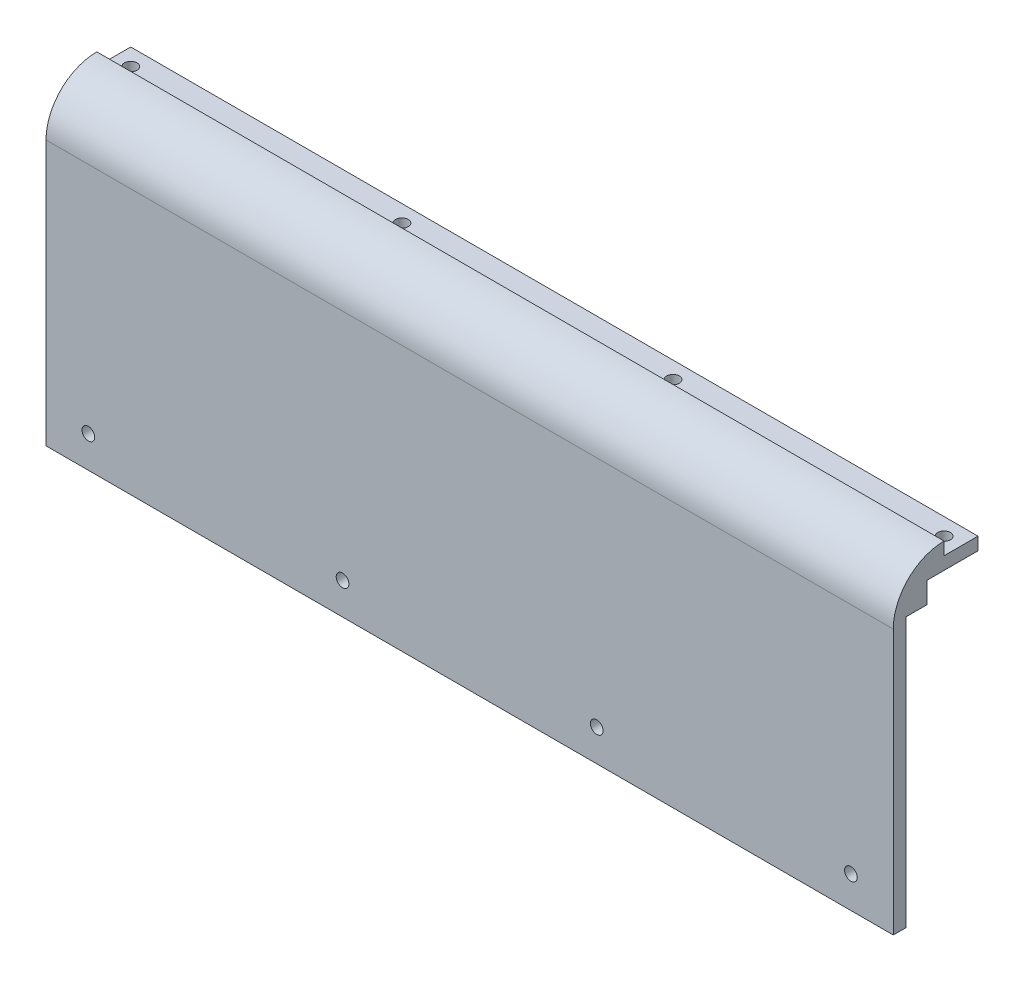
SolidWorks part; units mm, degrees
ref_plane "Front Plane" through (0, 0, 0) normal (0, 0, 1) x (1, 0, 0)
ref_plane "Top Plane" through (0, 0, 0) normal (0, 1, 0) x (1, 0, 0)
ref_plane "Right Plane" through (0, 0, 0) normal (1, 0, 0) x (0, 0, -1)
sketch "Sketch1" plane through (0, 0, 0) normal (0, 1, 0) x (1, 0, 0)
  line L1 (-100, -10) -> (100, -10)
  line L2 (-100, -10) -> (-100, 10)
  line L3 (-100, 10) -> (100, 10)
  line L4 (100, -10) -> (100, 10)
  line L5 (-100, -10) -> (100, 10) construction
  line L6 (-100, 10) -> (100, -10) construction
  point P0 (0, 0)
  dimension "D1" = 200
  dimension "D2" = 20
extrude "Boss-Extrude1" add sketch "Sketch1" along normal blind 3
sketch "Sketch2" plane through (0, 3, 0) normal (0, 1, 0) x (1, 0, 0)
  line L0 (100, 10) -> (-100, 10) construction
  line L1 (-100, 10) -> (-100, -10) construction
  circle A0 centre (-96, 6) radius 1.5
  dimension "D1" = 3
  dimension "D2" = 4
  dimension "D3" = 4
extrude "Cut-Extrude1" cut sketch "Sketch2" against normal up to next
pattern_linear "LPattern1" count 4 spacing 64 along (1, 0, 0) of "Cut-Extrude1"
sketch "Sketch3" plane through (0, 0, 0) normal (0, -1, 0) x (1, 0, 0)
  line L0 (100, 10) -> (100, -10) construction
  line L1 (-100, 10) -> (100, 10)
  line L2 (-100, 10) -> (-100, 7)
  line L3 (-100, 7) -> (100, 7)
  line L4 (100, 10) -> (100, 7)
  dimension "D1" = 3
extrude "Boss-Extrude2" add sketch "Sketch3" along normal blind 68.54
sketch "Sketch4" plane through (0, 0, 7) normal (0, 0, -1) x (-1, 0, 0)
  line L0 (100, -68.54) -> (100, 0) construction
  line L1 (-100, 0) -> (100, 0)
  line L2 (-100, 0) -> (-100, -5)
  line L3 (-100, -5) -> (100, -5)
  line L4 (100, 0) -> (100, -5)
  dimension "D1" = 5
extrude "Boss-Extrude3" add sketch "Sketch4" along normal blind 5
sketch "Sketch5" plane through (0, 3, 0) normal (0, 1, 0) x (1, 0, 0)
  line L1 (-100, -10) -> (100, -10)
  line L2 (-100, -10) -> (-100, 2)
  line L3 (-100, 2) -> (100, 2)
  line L4 (100, -10) -> (100, 2)
  dimension "D1" = 12
extrude "Boss-Extrude4" add sketch "Sketch5" along normal blind 3
fillet "Fillet4" radius 12 1 edges at (0, 6, 10)
sketch "Sketch6" plane through (0, 0, 7) normal (0, 0, -1) x (-1, 0, 0)
  line L0 (100, -68.54) -> (-100, -68.54) construction
  line L1 (100, -5) -> (97, -5)
  line L2 (100, -5) -> (100, -68.54)
  line L3 (100, -68.54) -> (97, -68.54)
  line L4 (97, -5) -> (97, -68.54)
  dimension "D1" = 3
extrude "Boss-Extrude5" add sketch "Sketch6" along normal blind 20
sketch "Sketch7" plane through (-100, 0, 0) normal (-1, 0, 0) x (0, 0, 1)
  line L0 (-13, -5) -> (2, -5) construction
  line L1 (10, -6) -> (10, -68.54) construction
  circle A0 centre (-5, -10.27) radius 1.5
  circle A1 centre (-5, -55.27) radius 1.5
  dimension "D1" = 3
  dimension "D2" = 3
  dimension "D3" = 45
  dimension "D4" = 5.27
  dimension "D5" = 15
extrude "Cut-Extrude2" cut sketch "Sketch7" against normal up to next
sketch "Sketch8" plane through (0, 0, 10) normal (0, 0, 1) x (1, 0, 0)
  line L0 (100, -68.54) -> (-100, -68.54) construction
  line L1 (-100, -6) -> (-100, -68.54) construction
  circle A0 centre (-90, -61.04) radius 1.5
  dimension "D2" = 3
  dimension "D1" = 7.5
  dimension "D3" = 10
extrude "Cut-Extrude3" cut sketch "Sketch8" against normal up to next
pattern_linear "LPattern2" count 4 spacing 60 along (1, 0, 0) of "Cut-Extrude3"
